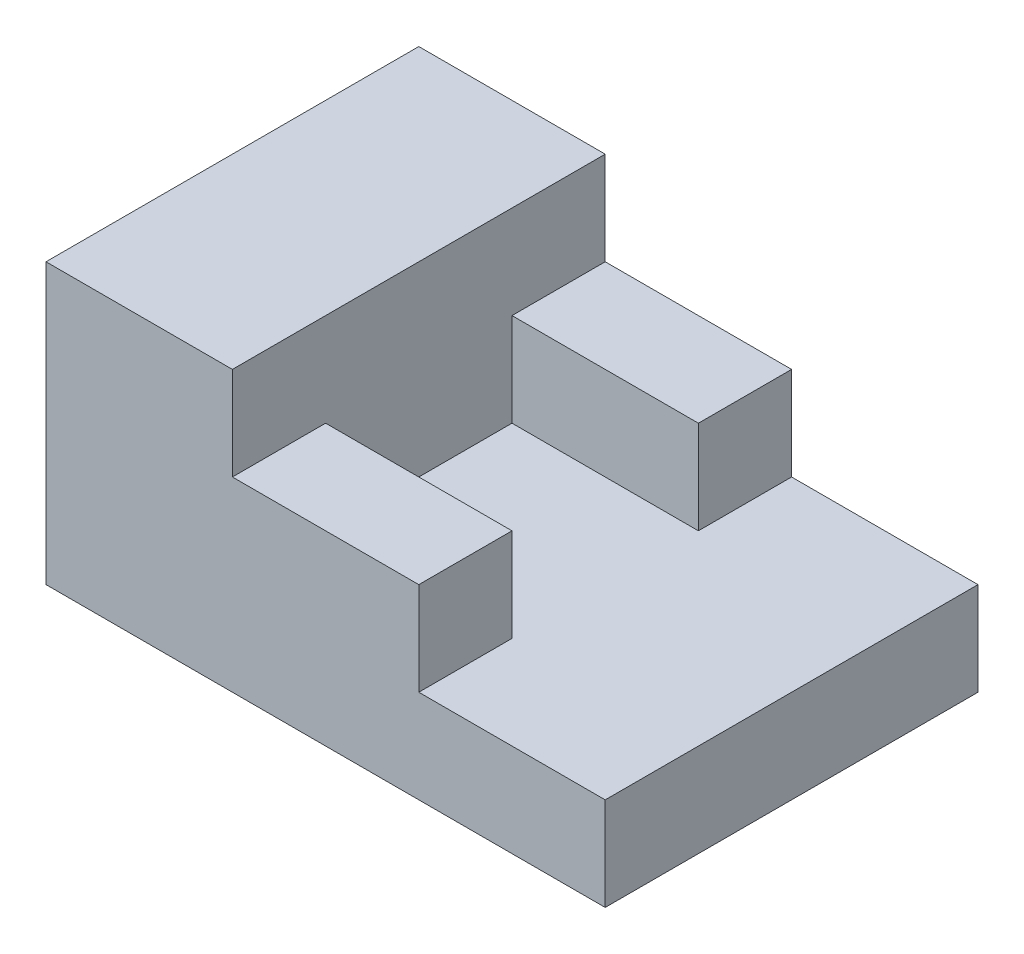
SolidWorks part; units mm, degrees
ref_plane "前基準面" through (0, 0, 0) normal (0, 0, 1) x (1, 0, 0)
ref_plane "上基準面" through (0, 0, 0) normal (0, 1, 0) x (1, 0, 0)
ref_plane "右基準面" through (0, 0, 0) normal (1, 0, 0) x (0, 0, -1)
sketch "草圖1" plane through (0, 0, 0) normal (0, 1, 0) x (1, 0, 0)
  line L0 (-5, 10) -> (-5, -10)
  line L1 (-15, -10) -> (15, -10)
  line L2 (-15, -10) -> (-15, 10)
  line L3 (-15, 10) -> (15, 10)
  line L4 (15, -10) -> (15, 10)
  line L5 (-15, -10) -> (15, 10) construction
  line L6 (-15, 10) -> (15, -10) construction
  line L7 (-5, -10) -> (-5, -5)
  line L8 (-5, -5) -> (5, -5)
  line L9 (5, -5) -> (5, -10)
  line L10 (-5, 5) -> (5, 5)
  line L11 (5, 5) -> (5, 10)
  point P0 (0, 0)
  dimension "D1" = 30
  dimension "D2" = 20
  dimension "D3" = 10
  dimension "D4" = 10
  dimension "D5" = 10
  dimension "D6" = 5
  dimension "D7" = 5
extrude "填料-伸長1" add sketch "草圖1" along normal blind 5 contours L11 L10 L0 L8 L9 L1 L4 L3 | L9 L8 L0 L1 | L3 L2 L1 L0 | L10 L11 L3 L0 region at (0, 0, -7.5) region at (-10, 0, 0) region at (6.6667, 0, 0) region at (0, 0, 7.5)
extrude "填料-伸長2" add sketch "草圖1<3>" along normal blind 10 contours L10 L11 L3 L0 | L9 L8 L0 L1 | L3 L2 L1 L0 region at (0, 0, -7.5) region at (-10, 0, 0) region at (0, 0, 7.5)
sketch "草圖1<3>" plane through (0, 0, 0) normal (0, 1, 0) x (1, 0, 0) same geometry as "草圖1"
extrude "填料-伸長3" add sketch "草圖1<4>" along normal blind 15 contours L3 L2 L1 L0 region at (-10, 0, 0)
sketch "草圖1<4>" plane through (0, 0, 0) normal (0, 1, 0) x (1, 0, 0) same geometry as "草圖1"
scale "縮放比例1" scale about centroid uniform scaling yes scale factor 0.2
